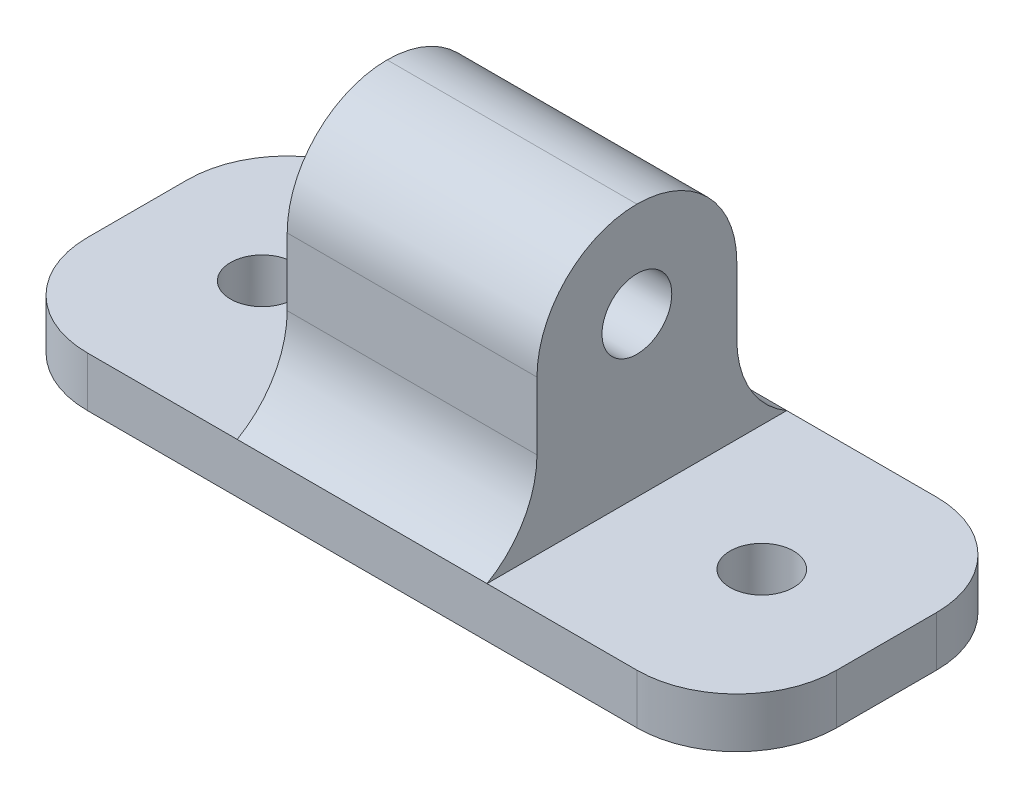
SolidWorks part; units mm, degrees
ref_plane "Front" through (0, 0, 0) normal (0, 0, 1) x (1, 0, 0)
ref_plane "Top" through (0, 0, 0) normal (0, 1, 0) x (1, 0, 0)
ref_plane "Right" through (0, 0, 0) normal (1, 0, 0) x (0, 0, -1)
sketch "Sketch1" plane through (0, 0, 0) normal (0, 1, 0) x (1, 0, 0)
  line L1 (-37.5, -15) -> (37.5, -15)
  line L2 (-37.5, -15) -> (-37.5, 15)
  line L3 (-37.5, 15) -> (37.5, 15)
  line L4 (37.5, -15) -> (37.5, 15)
  line L5 (-37.5, -15) -> (37.5, 15) construction
  line L6 (-37.5, 15) -> (37.5, -15) construction
  point P0 (0, 0)
  dimension "D1" = 30
  dimension "D2" = 75
extrude "Boss-Extrude1" add sketch "Sketch1" along normal blind 5
sketch "Sketch2" plane through (0, 5, 0) normal (0, 1, 0) x (1, 0, 0)
  line L1 (-12.5, -10) -> (12.5, -10)
  line L2 (-12.5, -10) -> (-12.5, 10)
  line L3 (-12.5, 10) -> (12.5, 10)
  line L4 (12.5, -10) -> (12.5, 10)
  line L5 (-12.5, -10) -> (12.5, 10) construction
  line L6 (-12.5, 10) -> (12.5, -10) construction
  point P0 (0, 0)
  dimension "D1" = 25
  dimension "D2" = 20
extrude "Boss-Extrude3" add sketch "Sketch2" along normal blind 25.4
sketch "Sketch4" plane through (0, 5, 0) normal (0, 1, 0) x (1, 0, 0)
  line L0 (-12.5, 0) -> (-37.5, 0) construction
  line L1 (-12.5, 10) -> (-12.5, -10) construction
  line L2 (-37.5, 15) -> (-37.5, -15) construction
  line L3 (12.5, 0) -> (37.5, 0) construction
  line L4 (12.5, -10) -> (12.5, 10) construction
  line L5 (37.5, -15) -> (37.5, 15) construction
  point P12 (-25, 0)
  point P13 (25, 0)
sketch "Sketch3" plane through (12.5, 0, 0) normal (1, 0, 0) x (0, 0, -1)
  line L0 (10, 20.875) -> (-10, 20.875) construction
  line L1 (10, 30.4) -> (10, 5) construction
  line L2 (-10, 30.4) -> (-10, 5) construction
  line L3 (-10, 30.4) -> (10, 30.4) construction
  circle A0 centre (0, 20.875) radius 3.4925
  dimension "D1" = 6.985
  dimension "D2" = 9.525
extrude "Cut-Extrude1" cut sketch "Sketch3" against normal through all
hole_wizard "1/4 (0.25) Diameter Hole2" positions "Sketch9" profile "Sketch10" hole size "1/4" standard "ANSI Inch" end condition up to next
sketch "Sketch9" plane through (0, 5, 0) normal (0, 1, 0) x (1, 0, 0)
  point P0 (-25, 0)
  point P3 (25, 0)
sketch "Sketch10" plane through (-25, 5, 0) normal (1, 0, 0) x (0, 0, 1)
  line L0 (0, 0) -> (0, 5)
  line L1 (0, 5) -> (3.175, 5)
  line L2 (3.175, 5) -> (3.175, 0)
  line L5 (3.175, 0) -> (0, 0)
  line L11 (0, -6.35) -> (0, 107.95) construction
  dimension "Thru Hole Dia." = 6.35
  dimension "Thru Hole Depth" = 5
fillet "Fillet2" radius 10 8 edges at (-37.5, 2.5, -15) (-37.5, 2.5, 15) (0, 5, 10) (0, 30.4, 10) (0, 30.4, -10) (0, 5, -10) (37.5, 2.5, 15) (37.5, 2.5, -15)
